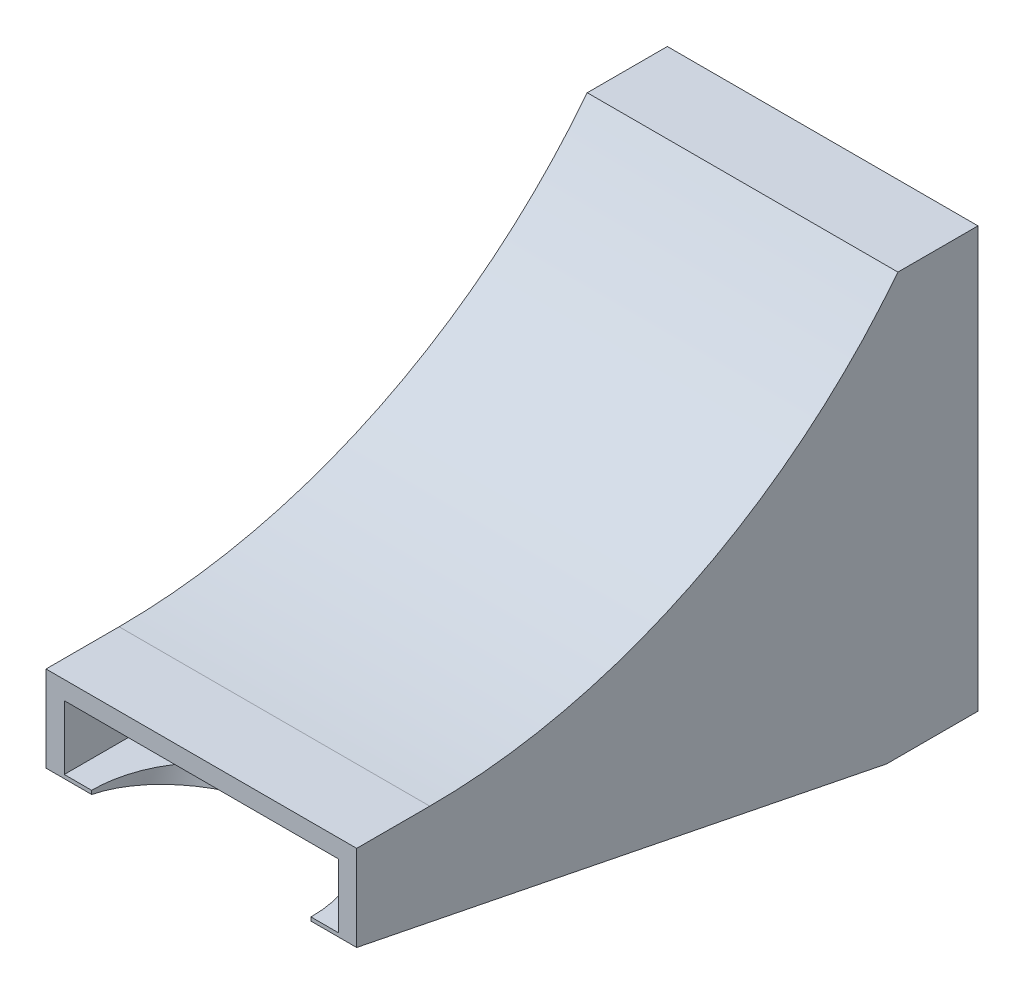
SolidWorks part; units mm, degrees
ref_plane "Front Plane" through (0, 0, 0) normal (0, 0, 1) x (1, 0, 0)
ref_plane "Top Plane" through (0, 0, 0) normal (0, 1, 0) x (1, 0, 0)
ref_plane "Right Plane" through (0, 0, 0) normal (1, 0, 0) x (0, 0, -1)
sketch "Sketch1" plane through (0, 0, 0) normal (0, 0, 1) x (1, 0, 0)
  line L1 (-7.5, 10.5) -> (7.5, 10.5)
  line L2 (-7.5, 10.5) -> (-7.5, -10.5)
  line L3 (-7.5, -10.5) -> (7.5, -10.5)
  line L4 (7.5, 10.5) -> (7.5, -10.5)
  line L5 (-7.5, 10.5) -> (7.5, -10.5) construction
  line L6 (-7.5, -10.5) -> (7.5, 10.5) construction
  line L7 (-8.5, -11.5) -> (8.5, -11.5)
  line L8 (-8.5, -11.5) -> (-8.5, 11.5)
  line L9 (-8.5, 11.5) -> (8.5, 11.5)
  line L10 (8.5, -11.5) -> (8.5, 11.5)
  line L11 (-8.5, -11.5) -> (8.5, 11.5) construction
  line L12 (-8.5, 11.5) -> (8.5, -11.5) construction
  point P0 (0, 0)
  point P6 (0, 0)
  dimension "D1" = 21
  dimension "D2" = 15
  dimension "D3" = 1
  dimension "D4" = 1
extrude "Boss-Extrude1" add sketch "Sketch1" along normal blind 30
sketch "Sketch2" plane through (8.5, 0, 0) normal (1, 0, 0) x (0, 0, -1)
  line L0 (0, -11.5) -> (0, 11.5) construction
  line L1 (-30, 11.5) -> (0, 11.5) construction
  circle A0 centre (-30, 31.5) radius 32.5
  dimension "D3" = 65
  dimension "D1" = 30
  dimension "D2" = 20
extrude "Cut-Extrude1" cut sketch "Sketch2" against normal through all
sketch "Sketch3" plane through (8.5, 0, 0) normal (1, 0, 0) x (0, 0, -1)
  line L0 (-30, -1) -> (-30, -2)
  line L1 (-4.3826, 11.5) -> (-3.1253, 11.5)
  line L2 (-4.3826, 11.5) -> (0, 11.5) construction
  arc A0 (-30, -2) -> (-3.1253, 11.5) centre (-30, 31.5) ccw
  arc A1 (-30, -1) -> (-4.3826, 11.5) centre (-30, 31.5) ccw construction
  arc A2 (-30, -1) -> (-4.3826, 11.5) centre (-30, 31.5) ccw
  dimension "D1" = 1
extrude "Boss-Extrude2" add sketch "Sketch3" against normal through all
sketch "Sketch4" plane through (-8.5, 0, 0) normal (-1, 0, 0) x (0, 0, 1)
  line L0 (5, -11.5) -> (30, -6.5)
  line L1 (30, -11.5) -> (0, -11.5) construction
  line L3 (30, -6.5) -> (30, -11.5)
  line L4 (30, -11.5) -> (5, -11.5)
  dimension "D1" = 5
  dimension "D2" = 25
extrude "Cut-Extrude2" cut sketch "Sketch4" against normal through all
sketch "Sketch5" plane through (-8.5, 0, 0) normal (-1, 0, 0) x (0, 0, 1)
  line L0 (5, -11.5) -> (30, -6.5)
  line L1 (30, -6.5) -> (30, -5.5)
  line L2 (30, -1) -> (30, -6.5) construction
  line L3 (30, -5.5) -> (0, -11.5)
  line L5 (0, -11.5) -> (5, -11.5)
  line L6 (5, -11.5) -> (0, -11.5) construction
extrude "Boss-Extrude3" add sketch "Sketch5" against normal through all
sketch "Sketch6" plane through (0, 0, 30) normal (0, 0, 1) x (1, 0, 0)
  line L0 (-8.5, -1) -> (8.5, -1)
  line L1 (8.5, -1) -> (8.5, -6.5)
  line L2 (8.5, -6.5) -> (-8.5, -6.5)
  line L3 (-8.5, -6.5) -> (-8.5, -1)
  line L4 (-7.5, -2) -> (-7.5, -5.5)
  line L5 (-7.5, -5.5) -> (7.5, -5.5)
  line L6 (7.5, -5.5) -> (7.5, -2)
  line L7 (7.5, -2) -> (-7.5, -2)
extrude "Boss-Extrude4" add sketch "Sketch6" along normal blind 4
sketch "Sketch7" plane through (-8.5, 0, 0) normal (-1, 0, 0) x (0, 0, 1)
  line L0 (24, -7.7) -> (34, -5.7)
  line L2 (34, -1) -> (34, -6.5) construction
  line L3 (34, -5.7) -> (34, -7.7)
  line L4 (34, -7.7) -> (24, -7.7)
  line L5 (30, -6.5) -> (5, -11.5) construction
  dimension "D1" = 2
extrude "Cut-Extrude3" cut sketch "Sketch7" against normal through all
sketch "Sketch8" plane through (0, -12.0192, 2.4038) normal (0, -0.9806, 0.1961) x (1, 0, 0)
  line L0 (8.5, 32.2219) -> (-8.5, 32.2219) construction
  circle A0 centre (0, 32.2219) radius 6
  dimension "D1" = 12
extrude "Cut-Extrude4" cut sketch "Sketch8" against normal up to next
